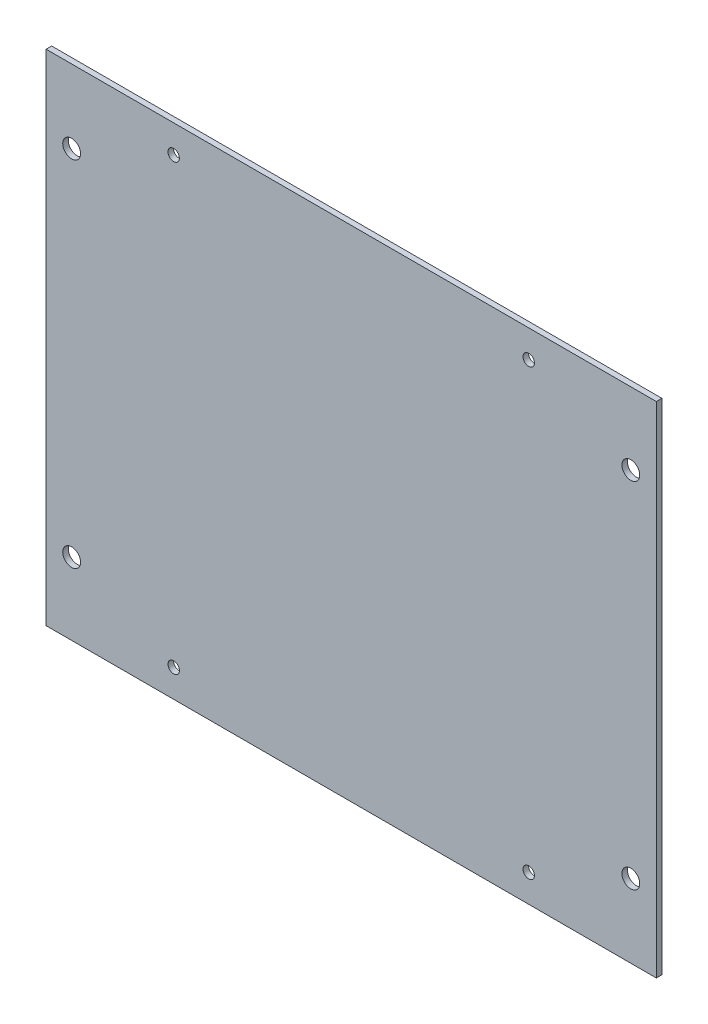
SolidWorks part; units mm, degrees
material "Perspex (TM) GS Acrylic Cast Sheet"
ref_plane "Front Plane" through (0, 0, 0) normal (0, 0, 1) x (1, 0, 0)
ref_plane "Top Plane" through (0, 0, 0) normal (0, 1, 0) x (1, 0, 0)
ref_plane "Right Plane" through (0, 0, 0) normal (1, 0, 0) x (0, 0, -1)
sketch "Sketch1" plane through (0, 0, 0) normal (0, 0, 1) x (1, 0, 0)
  line L1 (-457.2, -304.8) -> (457.2, -304.8)
  line L2 (-457.2, -304.8) -> (-457.2, 304.8)
  line L3 (-457.2, 304.8) -> (457.2, 304.8)
  line L4 (457.2, -304.8) -> (457.2, 304.8)
  line L5 (0, 304.8) -> (0, -304.8) construction
  line L6 (-457.2, 0) -> (457.2, 0) construction
  point P0 (0, 0)
  point P4 (-320.04, 0)
  point P5 (320.04, 0)
  point P6 (0, 213.36)
  point P7 (0, -213.36)
  dimension "Length" = 914.4
  dimension "Width" = 609.6
  dimension "Break" = 137.16
  dimension "D2" = 137.16
  dimension "D1" = 91.44
  dimension "D3" = 91.44
sketch "Sketch2" plane through (0, 0, 0) normal (1, 0, 0) x (0, 0, -1)
  line L0 (-0.7938, -304.8) -> (0.7938, -304.8)
  dimension "Thickness" = 1.5875
sketch "Sketch3" plane through (0, 0, 0) normal (0, 0, 1) x (1, 0, 0)
  line L0 (-457.2, -304.8) -> (-457.2, 304.8) construction
  line L1 (-457.2, -304.8) -> (457.2, -304.8) construction
  line L2 (457.2, -304.8) -> (457.2, 304.8) construction
  line L3 (-457.2, 304.8) -> (457.2, 304.8) construction
  line L4 (-457.2, -304.8) -> (-457.2, 304.8)
  line L5 (-457.2, -304.8) -> (457.2, -304.8)
  line L6 (457.2, -304.8) -> (457.2, 304.8)
  line L7 (-457.2, 304.8) -> (457.2, 304.8)
extrude "Boss-Extrude1" add sketch "Sketch3" along normal mid plane 1.5875
sketch "Sketch4" plane through (0, 0, -0.7937) normal (0, 0, -1) x (-1, 0, 0)
  line L0 (393.5597, -82.9526) -> (218.9347, -82.9526)
  line L1 (218.9347, -82.9526) -> (218.9347, 59.9224)
  line L2 (218.9347, 59.9224) -> (393.5597, 59.9224)
  line L3 (393.5597, 59.9224) -> (393.5597, -82.9526)
extrude "Cut-Extrude1" cut sketch "Sketch4" against normal blind 2.54 flip side to cut
hole_wizard "#4 Clearance Hole1" positions "Sketch9" profile "Sketch10" hole size "#4" standard "ANSI Inch" end condition through all
sketch "Sketch9" plane through (0, 0, -0.7937) normal (0, 0, -1) x (-1, 0, 0)
  line L0 (356.7455, 51.9595) -> (357.3855, 51.9595) construction
  point P0 (255.4472, -75.0151)
  point P6 (357.0655, 51.9595)
  point P16 (357.0472, -75.0151)
  point P28 (255.4472, 51.9849)
sketch "Sketch10" plane through (-255.4472, -75.0151, -0.7937) normal (1, 0, 0) x (0, 1, 0)
  line L0 (0, 0) -> (0, 1.5875)
  line L1 (0, 1.5875) -> (1.6319, 1.5875)
  line L2 (1.6319, 1.5875) -> (1.6319, 0)
  line L5 (1.6319, 0) -> (0, 0)
  line L11 (0, -6.35) -> (0, 107.95) construction
  dimension "Thru Hole Dia." = 3.2639
  dimension "Thru Hole Depth" = 1.5875
hole_wizard "#10 Clearance Hole1" positions "Sketch11" profile "Sketch12" hole size "#10" standard "ANSI Inch" end condition through all
sketch "Sketch11" plane through (0, 0, -0.7937) normal (0, 0, -1) x (-1, 0, 0)
  point P0 (226.2372, -61.9595)
  point P3 (226.2372, 39.2846)
  point P6 (386.2572, 38.9293)
  point P9 (386.2572, -62.3148)
sketch "Sketch12" plane through (-226.2372, -61.9595, -0.7937) normal (1, 0, 0) x (0, 1, 0)
  line L0 (0, 0) -> (0, 1.5875)
  line L1 (0, 1.5875) -> (2.5527, 1.5875)
  line L2 (2.5527, 1.5875) -> (2.5527, 0)
  line L5 (2.5527, 0) -> (0, 0)
  line L11 (0, -6.35) -> (0, 107.95) construction
  dimension "Thru Hole Dia." = 5.1054
  dimension "Thru Hole Depth" = 1.5875
equation "\"D1@Boss-Extrude1\"=\"thickness@sketch2\""
equation "\"Break@Sketch1\" = \"Length@Sketch1\" * 0.15"
equation "\"D2@Sketch1\" = \"Break@Sketch1\""
equation "\"D1@Sketch1\"=\"Width@Sketch1\"*0.15"
equation "\"D3@Sketch1\"=\"D1@Sketch1\""
